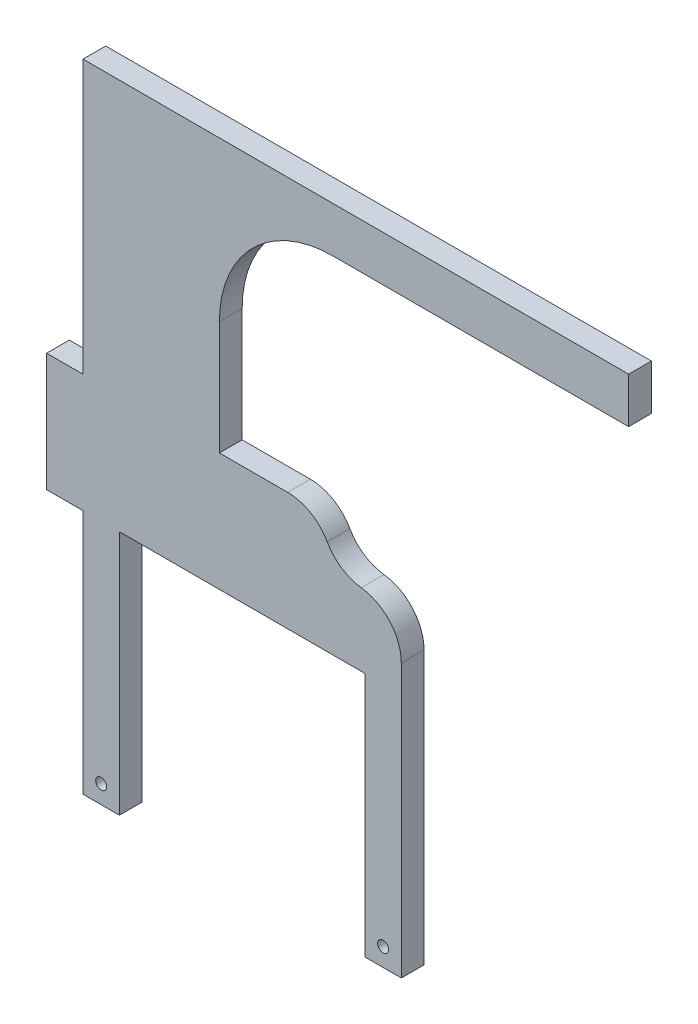
SolidWorks part; units mm, degrees
ref_plane "Plan de face" through (0, 0, 0) normal (0, 0, 1) x (1, 0, 0)
ref_plane "Plan de dessus" through (0, 0, 0) normal (0, 1, 0) x (1, 0, 0)
ref_plane "Plan de droite" through (0, 0, 0) normal (1, 0, 0) x (0, 0, -1)
sketch "Esquisse1" plane through (0, 0, 0) normal (0, 0, 1) x (1, 0, 0)
  line L36 (0, 0) -> (0, 54)
  line L41 (0, 140) -> (120, 140)
  line L42 (120, 140) -> (120, 130)
  line L43 (120, 130) -> (30, 130)
  line L44 (30, 130) -> (30, 80)
  line L45 (30, 80) -> (70, 80)
  line L46 (70, 80) -> (70, 0)
  line L47 (70, 0) -> (62, 0)
  line L48 (62, 0) -> (62, 54)
  line L49 (62, 54) -> (8, 54)
  line L50 (0, 0) -> (8, 0)
  line L51 (8, 0) -> (8, 54)
  line L52 (0, 80) -> (-8, 80)
  line L53 (-8, 80) -> (-8, 54)
  line L54 (-8, 54) -> (0, 54)
  line L55 (0, 80) -> (0, 140)
  dimension "D2" = 8
  dimension "D3" = 54
  dimension "D4" = 8
  dimension "D5" = 10
  dimension "D6" = 140
  dimension "D7" = 8
  dimension "D8" = 120
  dimension "D10" = 90
  dimension "D11" = 50
  dimension "D12" = 54
extrude "Boss.-Extru.1" add sketch "Esquisse1" along normal blind 5
sketch "Esquisse2" plane through (0, 0, 5) normal (0, 0, 1) x (1, 0, 0)
  line L0 (0, 0) -> (8, 0) construction
  line L1 (8, 0) -> (8, 54) construction
  line L2 (62, 0) -> (70, 0) construction
  line L3 (70, 0) -> (70, 80) construction
  circle A0 centre (4, 4) radius 1
  circle A1 centre (66, 4) radius 1
  dimension "D1" = 4
  dimension "D3" = 2
  dimension "D6" = 2
  dimension "D2" = 4
  dimension "D4" = 4
  dimension "D5" = 4
fillet "Congé1" [suppressed] radius 10
fillet "Congé2" radius 25 1 edges at (30, 130, 2.5)
sketch "Esquisse5" plane through (0, 0, 5) normal (0, 0, 1) x (1, 0, 0)
  line L1 (70, 80) -> (55, 80)
  line L2 (70, 80) -> (70, 70)
  line L3 (70, 70) -> (55, 70)
  line L4 (55, 80) -> (55, 70)
  dimension "D1" = 15
  dimension "D2" = 10
extrude "Enlèv. mat.-Extru.1" cut sketch "Esquisse5" against normal up to surface (5 mm away) up to face at (36.1072, 69.7752, 0)
sketch "Esquisse6" plane through (0, 0, 5) normal (0, 0, 1) x (1, 0, 0)
  line L0 (55, 130) -> (120, 130) construction
  line L1 (120, 140) -> (112, 140)
  line L2 (120, 140) -> (120, 130)
  line L3 (120, 130) -> (112, 130)
  line L4 (112, 140) -> (112, 130)
  dimension "D1" = 8
extrude "Enlèv. mat.-Extru.2" [suppressed] cut sketch "Esquisse6" against normal up to surface (5 mm away) up to face at (38.0959, 69.7988, 0)
fillet "Congé3" radius 10 2 edges at (70, 70, 2.5) (55, 80, 2.5)
fillet "Congé4" radius 10 1 edges at (55, 70, 2.5)
sketch "Esquisse7" plane through (0, 0, 5) normal (0, 0, 1) x (1, 0, 0)
  line L0 (0, 54) -> (0, 0) construction
  line L1 (120, 140) -> (0, 140)
  line L2 (120, 140) -> (120, 80)
  line L3 (120, 80) -> (0, 80)
  line L4 (0, 140) -> (0, 80)
  line L5 (45, 80) -> (30, 80) construction
extrude "Enlèv. mat.-Extru.3" [suppressed] cut sketch "Esquisse7" against normal up to surface (5 mm away) up to face at (38.7849, 69.6492, 0)
sketch "Esquisse8" [suppressed] plane through (0, 0, 5) normal (0, 0, 1) x (1, 0, 0)
  line L5 (0, 80) -> (-15, 80)
  line L6 (-15, 80) -> (-15, 54)
  line L7 (-15, 54) -> (0, 54)
  line L8 (0, 80) -> (0, 0) construction
  line L9 (8, 54) -> (62, 54) construction
  line L10 (0, 80) -> (0, 54)
  line L18 (45, 80) -> (0, 80)
  line L19 (0, 80) -> (0, 0)
  line L20 (0, 0) -> (8, 0)
  line L21 (8, 0) -> (8, 54)
  line L22 (8, 54) -> (62, 54)
  line L23 (62, 54) -> (62, 0)
  line L24 (62, 0) -> (70, 0)
  line L25 (70, 0) -> (70, 60)
  line L26 (45, 80) -> (0, 80)
  line L27 (0, 54) -> (0, 0)
  line L28 (0, 0) -> (8, 0)
  line L29 (8, 0) -> (8, 54)
  line L30 (8, 54) -> (62, 54)
  line L31 (62, 54) -> (62, 0)
  line L32 (62, 0) -> (70, 0)
  line L33 (70, 0) -> (70, 60)
  arc A3 (70, 60) -> (61.2017, 69.9275) centre (60, 60) ccw
  arc A4 (53.7017, 74.9275) -> (61.2017, 69.9275) centre (62.4034, 79.8551) ccw
  arc A5 (53.7017, 74.9275) -> (45, 80) centre (45, 70) ccw
  arc A6 (70, 60) -> (61.2017, 69.9275) centre (60, 60) ccw
  arc A7 (53.7017, 74.9275) -> (61.2017, 69.9275) centre (62.4034, 79.8551) ccw
  arc A8 (53.7017, 74.9275) -> (45, 80) centre (45, 70) ccw
  dimension "D1" = 15
  dimension "D2" = 0
extrude "Enlèv. mat.-Extru.5" cut sketch "Esquisse2" against normal blind 10
hole_wizard "Dégagement M21" positions "Esquisse3" profile "Esquisse4" hole size "M2" standard "ISO" end condition through all
sketch "Esquisse3" plane through (0, 0, 5) normal (0, 0, 1) x (1, 0, 0)
  point P0 (4, 4)
  point P3 (66, 4)
sketch "Esquisse4" plane through (4, 4, 5) normal (1, 0, 0) x (0, -1, 0)
  line L0 (0, 0) -> (0, 5)
  line L1 (0, 5) -> (1.2, 5)
  line L2 (1.2, 5) -> (1.2, 0)
  line L5 (1.2, 0) -> (0, 0)
  line L11 (0, -6.35) -> (0, 107.95) construction
  dimension "Diamètre du perçage jusqu'au prochain" = 2.4
  dimension "Profondeur du perçage jusqu'au prochain" = 5
